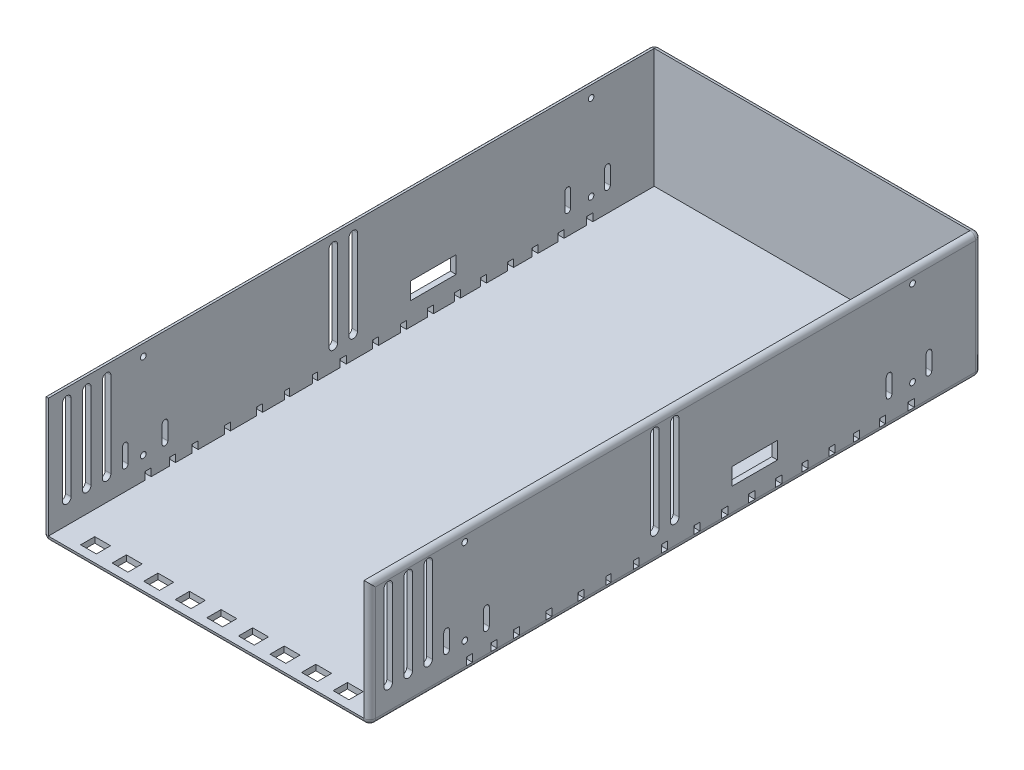
SolidWorks part; units mm, degrees
ref_plane "Front Plane" through (0, 0, 0) normal (0, 0, 1) x (1, 0, 0)
ref_plane "Top Plane" through (0, 0, 0) normal (0, 1, 0) x (1, 0, 0)
ref_plane "Right Plane" through (0, 0, 0) normal (1, 0, 0) x (0, 0, -1)
sketch "Sketch1" plane through (0, 0, 0) normal (0, 1, 0) x (1, 0, 0)
  line L0 (0, 0) -> (115, 0)
  line L1 (115, 0) -> (115, 215)
  line L2 (115, 215) -> (0, 215)
  line L3 (0, 215) -> (0, 0)
  dimension "D1" = 215
extrude "Boss-Extrude1" add sketch "Sketch1" along normal blind 44
sketch "Sketch2" plane through (0, 44, 0) normal (0, 1, 0) x (1, 0, 0)
  line L0 (2, 213) -> (113, 213)
  line L1 (113, 213) -> (113, 0)
  line L2 (0, 0) -> (115, 0) construction
  line L3 (2, 213) -> (2, 0)
  line L4 (0, 215) -> (0, 0) construction
  line L5 (115, 215) -> (0, 215) construction
  dimension "D1" = 2
  dimension "D2" = 2
  dimension "D3" = 2
extrude "Cut-Extrude1" cut sketch "Sketch2" against normal blind 42 and the other way through all
sketch "Sketch3" plane through (115, 0, 0) normal (1, 0, 0) x (0, 0, -1)
  line L4 (127.3247, 10) -> (127.3247, 16)
  line L6 (5, 40) -> (5, 10)
  line L7 (8, 40) -> (8, 10)
  line L8 (12, 40) -> (12, 10)
  line L9 (15, 40) -> (15, 10)
  line L10 (19, 40) -> (19, 10)
  line L11 (22, 40) -> (22, 10)
  line L12 (26, 10) -> (26, 16)
  line L14 (28, 16) -> (28, 10)
  line L15 (40, 10) -> (40, 16)
  line L17 (42, 16) -> (42, 10)
  line L18 (98.689, 10) -> (98.689, 40)
  line L20 (101.689, 40) -> (101.689, 10)
  line L22 (105.689, 10) -> (105.689, 40)
  line L24 (108.689, 40) -> (108.689, 10)
  line L39 (127.3247, 10) -> (143.3247, 10)
  line L40 (127.3247, 16) -> (143.3247, 16)
  line L41 (143.3247, 16) -> (143.3247, 10)
  line L43 (197.5672, 10) -> (197.5672, 16)
  line L45 (195.5672, 16) -> (195.5672, 10)
  line L47 (183.5672, 10) -> (183.5672, 16)
  line L49 (181.5672, 16) -> (181.5672, 10)
  arc A0 (8, 40) -> (5, 40) centre (6.5, 40) ccw
  arc A1 (12, 40) -> (15, 40) centre (13.5, 40) cw
  arc A2 (19, 40) -> (22, 40) centre (20.5, 40) cw
  arc A3 (5, 10) -> (8, 10) centre (6.5, 10) ccw
  arc A4 (12, 10) -> (15, 10) centre (13.5, 10) ccw
  arc A5 (22, 10) -> (19, 10) centre (20.5, 10) cw
  arc A6 (26, 10) -> (28, 10) centre (27, 10) ccw
  arc A7 (28, 16) -> (26, 16) centre (27, 16) ccw
  arc A8 (40, 10) -> (42, 10) centre (41, 10) ccw
  arc A9 (42, 16) -> (40, 16) centre (41, 16) ccw
  arc A10 (98.689, 40) -> (101.689, 40) centre (100.189, 40) cw
  arc A11 (105.689, 40) -> (108.689, 40) centre (107.189, 40) cw
  arc A12 (98.689, 10) -> (101.689, 10) centre (100.189, 10) ccw
  arc A13 (105.689, 10) -> (108.689, 10) centre (107.189, 10) ccw
  arc A14 (181.5672, 16) -> (183.5672, 16) centre (182.5672, 16) cw
  arc A15 (181.5672, 10) -> (183.5672, 10) centre (182.5672, 10) ccw
  arc A16 (195.5672, 16) -> (197.5672, 16) centre (196.5672, 16) cw
  arc A17 (195.5672, 10) -> (197.5672, 10) centre (196.5672, 10) ccw
  dimension "D1" = 3
  dimension "D4" = 3
  dimension "D9" = 2
  dimension "D10" = 12
  dimension "D11" = 4
  dimension "D12" = 4
  dimension "D13" = 3
  dimension "D14" = 6
  dimension "D15" = 16
  dimension "D16" = 6
  dimension "D18" = 2
  dimension "D19" = 2
  dimension "D20" = 6
  dimension "D21" = 12
extrude "Cut-Extrude2" cut sketch "Sketch3" against normal through all both and the other way through all
sketch "Sketch5" plane through (0, 2, 0) normal (0, 1, 0) x (1, 0, 0)
  line L0 (10.325, 3) -> (15.875, 3)
  line L1 (60.275, 8) -> (60.275, 3)
  line L2 (60.275, 3) -> (54.725, 3)
  line L3 (21.425, 3) -> (21.425, 8)
  line L5 (54.725, 3) -> (54.725, 8)
  line L6 (10.325, 8) -> (10.325, 3)
  line L7 (15.875, 3) -> (15.875, 8)
  line L8 (15.875, 8) -> (10.325, 8)
  line L9 (21.425, 8) -> (26.975, 8)
  line L10 (26.975, 8) -> (26.975, 3)
  line L11 (26.975, 3) -> (21.425, 3)
  line L12 (32.525, 3) -> (32.525, 8)
  line L13 (32.525, 8) -> (38.075, 8)
  line L14 (38.075, 8) -> (38.075, 3)
  line L15 (38.075, 3) -> (32.525, 3)
  line L16 (43.625, 8) -> (49.175, 8)
  line L17 (49.175, 8) -> (49.175, 3)
  line L18 (49.175, 3) -> (43.625, 3)
  line L19 (43.625, 3) -> (43.625, 8)
  line L20 (54.725, 8) -> (60.275, 8)
  line L21 (65.825, 8) -> (65.825, 3)
  line L22 (65.825, 3) -> (71.375, 3)
  line L23 (71.375, 3) -> (71.375, 8)
  line L24 (71.375, 8) -> (65.825, 8)
  line L25 (76.925, 3) -> (82.475, 3)
  line L26 (82.475, 3) -> (82.475, 8)
  line L27 (82.475, 8) -> (76.925, 8)
  line L28 (76.925, 8) -> (76.925, 3)
  line L29 (88.025, 3) -> (93.575, 3)
  line L30 (93.575, 3) -> (93.575, 8)
  line L31 (93.575, 8) -> (88.025, 8)
  line L32 (88.025, 8) -> (88.025, 3)
  line L33 (99.125, 3) -> (104.675, 3)
  line L34 (104.675, 3) -> (104.675, 8)
  line L35 (104.675, 8) -> (99.125, 8)
  line L36 (99.125, 8) -> (99.125, 3)
  line L40 (2, 213) -> (2, 0) construction
  dimension "D1" = 5.55
  dimension "D2" = 5.55
  dimension "D3" = 8.325
extrude "Cut-Extrude3" cut sketch "Sketch5" against normal through all
fillet "Fillet2" radius 2 3 edges at (0, 0, -107.5) (115, 0, -107.5) (57.5, 0, -215)
fillet "Fillet3" radius 2 4 edges at (114.4142, 0.5858, -214.4142) (0.5858, 0.5858, -214.4142) (115, 23, -215) (0, 23, -215)
sketch "Sketch6" plane through (115, 0, 0) normal (1, 0, 0) x (0, 0, -1)
  circle A0 centre (33.3837, 9.9607) radius 1
  circle A1 centre (33.3837, 39.9747) radius 1
  circle A23 centre (190.8043, 9.9607) radius 1
  circle A24 centre (190.8043, 39.9747) radius 1
extrude "Cut-Extrude7" cut sketch "Sketch6" against normal through all
sketch "Sketch7" plane through (115, 0, 0) normal (1, 0, 0) x (0, 0, -1)
  line L0 (0, 2) -> (213, 2) construction
  line L1 (33.9962, 4.6906) -> (36.1401, 4.6906)
  line L2 (33.9962, 4.6906) -> (33.9962, 2)
  line L3 (33.9962, 2) -> (36.1401, 2)
  line L4 (36.1401, 4.6906) -> (36.1401, 2)
  line L6 (42.5717, 4.6906) -> (44.7155, 4.6906)
  line L7 (42.5717, 4.6906) -> (42.5717, 2)
  line L8 (42.5717, 2) -> (44.7155, 2)
  line L9 (44.7155, 4.6906) -> (44.7155, 2)
  line L14 (61.8664, 2) -> (64.0103, 2)
  line L15 (61.8664, 2) -> (61.8664, 4.6906)
  line L16 (61.8664, 4.6906) -> (64.0103, 4.6906)
  line L17 (64.0103, 2) -> (64.0103, 4.6906)
  line L18 (73.1982, 2) -> (75.3421, 2)
  line L19 (73.1982, 2) -> (73.1982, 4.6906)
  line L20 (73.1982, 4.6906) -> (75.3421, 4.6906)
  line L21 (75.3421, 2) -> (75.3421, 4.6906)
  line L22 (82.9987, 2) -> (84.8363, 2)
  line L23 (82.9987, 2) -> (82.9987, 4.6906)
  line L24 (82.9987, 4.6906) -> (84.8363, 4.6906)
  line L25 (84.8363, 2) -> (84.8363, 4.6906)
  line L26 (92.7992, 2) -> (94.6368, 2)
  line L27 (92.7992, 2) -> (92.7992, 4.6906)
  line L28 (92.7992, 4.6906) -> (94.6368, 4.6906)
  line L29 (94.6368, 2) -> (94.6368, 4.6906)
  line L34 (113.9316, 2) -> (116.0754, 2)
  line L35 (113.9316, 2) -> (113.9316, 4.6906)
  line L36 (113.9316, 4.6906) -> (116.0754, 4.6906)
  line L37 (116.0754, 2) -> (116.0754, 4.6906)
  line L42 (133.2263, 2) -> (135.3702, 2)
  line L43 (133.2263, 2) -> (133.2263, 4.6906)
  line L44 (133.2263, 4.6906) -> (135.3702, 4.6906)
  line L45 (135.3702, 2) -> (135.3702, 4.6906)
  line L46 (142.7206, 2) -> (144.8644, 2)
  line L47 (142.7206, 2) -> (142.7206, 4.6906)
  line L48 (142.7206, 4.6906) -> (144.8644, 4.6906)
  line L49 (144.8644, 2) -> (144.8644, 4.6906)
  line L50 (151.9085, 2) -> (154.0524, 2)
  line L51 (151.9085, 2) -> (151.9085, 4.6906)
  line L52 (151.9085, 4.6906) -> (154.0524, 4.6906)
  line L53 (154.0524, 2) -> (154.0524, 4.6906)
  line L54 (161.4028, 2) -> (163.5466, 2)
  line L55 (161.4028, 2) -> (161.4028, 4.6906)
  line L56 (161.4028, 4.6906) -> (163.5466, 4.6906)
  line L57 (163.5466, 2) -> (163.5466, 4.6906)
  line L58 (169.9782, 2) -> (172.1221, 2)
  line L59 (169.9782, 2) -> (169.9782, 4.6906)
  line L60 (169.9782, 4.6906) -> (172.1221, 4.6906)
  line L61 (172.1221, 2) -> (172.1221, 4.6906)
  line L62 (179.1662, 2) -> (181.3101, 2)
  line L63 (179.1662, 2) -> (179.1662, 4.6906)
  line L64 (179.1662, 4.6906) -> (181.3101, 4.6906)
  line L65 (181.3101, 2) -> (181.3101, 4.6906)
  line L66 (189.273, 2) -> (191.4168, 2)
  line L67 (189.273, 2) -> (189.273, 4.6906)
  line L68 (189.273, 4.6906) -> (191.4168, 4.6906)
  line L69 (191.4168, 2) -> (191.4168, 4.6906)
  line L70 (102.5997, 2) -> (104.7436, 2)
  line L71 (102.5997, 2) -> (102.5997, 4.6906)
  line L72 (102.5997, 4.6906) -> (104.7436, 4.6906)
  line L73 (104.7436, 2) -> (104.7436, 4.6906)
  line L74 (50.5346, 2) -> (52.6784, 2)
  line L75 (50.5346, 2) -> (50.5346, 4.6906)
  line L76 (50.5346, 4.6906) -> (52.6784, 4.6906)
  line L77 (52.6784, 2) -> (52.6784, 4.6906)
  line L78 (123.7321, 2) -> (125.8759, 2)
  line L79 (123.7321, 2) -> (123.7321, 4.6906)
  line L80 (123.7321, 4.6906) -> (125.8759, 4.6906)
  line L81 (125.8759, 2) -> (125.8759, 4.6906)
extrude "Cut-Extrude8" cut sketch "Sketch7" against normal through all
fillet "Fillet6" radius 2 10 edges at (0.5858, 44, -214.4142) (114.4142, 44, -214.4142) (0, 44, -106.5) (57.5, 44, -215) (115, 44, -106.5) (0.5858, 0.5858, 0) (114.4142, 0.5858, 0) (57.5, 0, 0) (0, 23, 0) (115, 23, 0)
